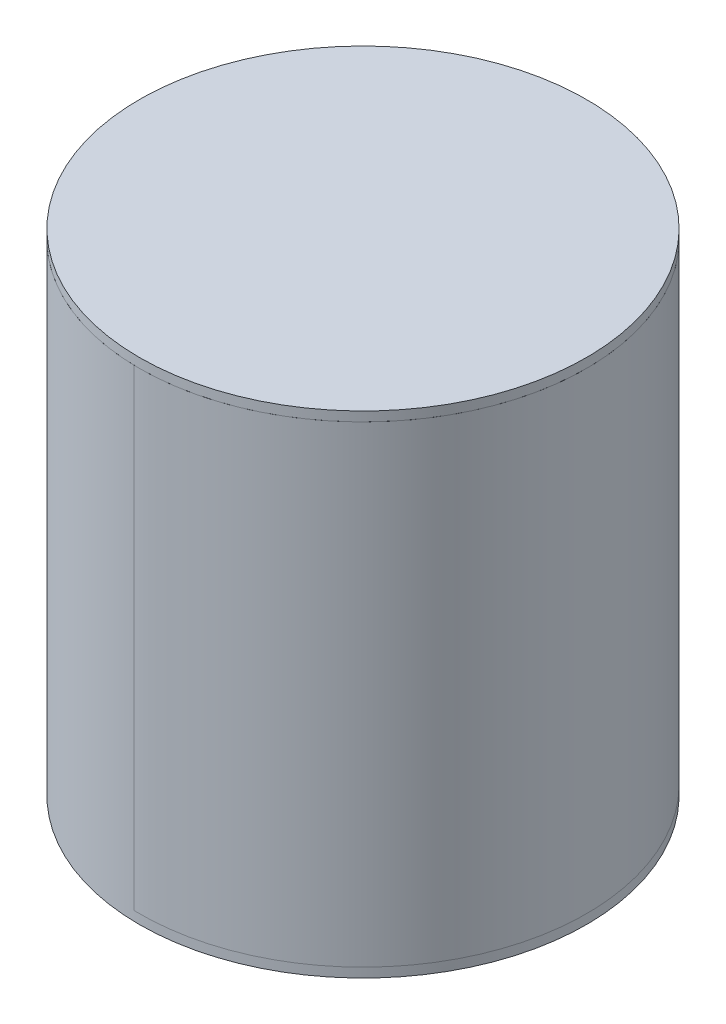
SolidWorks part; units mm, degrees
ref_plane "前基準面" through (0, 0, 0) normal (0, 0, 1) x (1, 0, 0)
ref_plane "上基準面" through (0, 0, 0) normal (0, 1, 0) x (1, 0, 0)
ref_plane "右基準面" through (0, 0, 0) normal (1, 0, 0) x (0, 0, -1)
sketch "second" plane through (0, 0, 0) normal (0, 1, 0) x (1, 0, 0)
  line L1 (-34, 34) -> (34, 34)
  line L2 (-34, 34) -> (-34, -34)
  line L3 (-34, -34) -> (34, -34)
  line L4 (34, 34) -> (34, -34)
  line L5 (-34, 34) -> (34, -34) construction
  line L6 (-34, -34) -> (34, 34) construction
  point P0 (0, 0)
  point P5 (-10, 30)
  point P6 (10, 30)
  point P8 (-30, 30)
  point P9 (-30, 0)
  point P10 (30, 30)
  point P11 (30, -30)
  point P12 (-30, -30)
  point P13 (0, 0)
  point P14 (-30, -15)
  point P15 (30, 10)
  point P16 (30, -10)
  dimension "D1" = 68
  dimension "D2" = 4
  dimension "D4" = 20
  dimension "D5" = 20
  dimension "D6" = 20
  dimension "D7" = 20
  dimension "D8" = 20
  dimension "D9" = 20
  dimension "D10" = 15
  dimension "D11" = 30
  dimension "D3" = 4
sketch "圓盤" plane through (0, 0, 0) normal (0, 1, 0) x (1, 0, 0)
  circle A0 centre (0, 0) radius 71
  dimension "D1" = 142
sketch "底座" plane through (0, 0, 0) normal (0, 1, 0) x (1, 0, 0)
  line L0 (0, 82.8964) -> (0, -77.2798) construction
  line L1 (-1.6763, 69.4798) -> (-1.7125, 70.9793)
  line L2 (1.6401, 67.9802) -> (1.6763, 69.4798)
  line L3 (-1.6763, -69.4798) -> (-1.7125, -70.9793)
  line L4 (0, 0) -> (43.8848, 0) construction
  line L6 (1.6401, -67.9802) -> (1.6763, -69.4798)
  circle A0 centre (0, 0) radius 71
  circle A1 centre (0, 0) radius 68
  arc A2 (1.6763, 69.4798) -> (-1.6763, 69.4798) centre (0, 0) ccw
  arc A3 (-1.6763, -69.4798) -> (1.6763, -69.4798) centre (0, 0) ccw
  point P13 (0, 71)
  dimension "D1" = 142
  dimension "D2" = 3
  dimension "D3" = 1.5
extrude "填料-伸長7" add sketch "底座" along normal blind 3 contours A1 | L3 A3 L6 A1 L2 A2 L1 A0 | A3 L3 A0 L1 A2 L2 A1 L6 region at (0, 0, -69.3405) region at (-0.0995, 0, -70.268) region at (0, 0, 0)
extrude "填料-伸長8" add sketch "底座<9>" along normal blind 150 from surface contours L3 A3 L6 A1 L2 A2 L1 A0 region at (0, 0, -69.3405) starting at face at (0, 3, 71)
sketch "底座<9>" plane through (0, 0, 0) normal (0, 1, 0) x (1, 0, 0) same geometry as "底座"
extrude "填料-伸長9" add sketch "底座<10>" along normal blind 150 from surface separate body contours A3 L3 A0 L1 A2 L2 A1 L6 region at (-0.0995, 0, -70.268) starting at face at (0.366, 3, 0)
sketch "底座<10>" plane through (0, 0, 0) normal (0, 1, 0) x (1, 0, 0) same geometry as "底座"
sketch "草圖7" plane through (0, 153, 0) normal (0, 1, 0) x (1, 0, 0)
  line L0 (-34, 34) -> (34, -34) construction
  circle A0 centre (0, 0) radius 69.5
extrude "除料-伸長2" cut sketch "草圖7" against normal blind 5 from surface starting at face at (-17.384, 153, 0)
sketch "草圖8" plane through (0, 153, 0) normal (0, 1, 0) x (1, 0, 0)
  circle A0 centre (0, 0) radius 71
  circle A1 centre (0, 0) radius 69.5
  arc M1 (-1.6763, 69.4798) -> (-1.6763, -69.4798) centre (0, 0) cw
extrude "填料-伸長11" add sketch "草圖8" along normal blind 3 separate body
extrude "填料-伸長14" add sketch "草圖8<7>" along normal up to surface (3 mm away) from surface contours A1 M1 region at (0, 153, 0) up to face at (0, 156, 71) starting at face at (35.2041, 148, 0)
sketch "草圖8<7>" plane through (0, 153, 0) normal (0, 1, 0) x (1, 0, 0) same geometry as "草圖8"
shell "薄殼4" thickness 1 removed face at (0, 148, 69.5)
